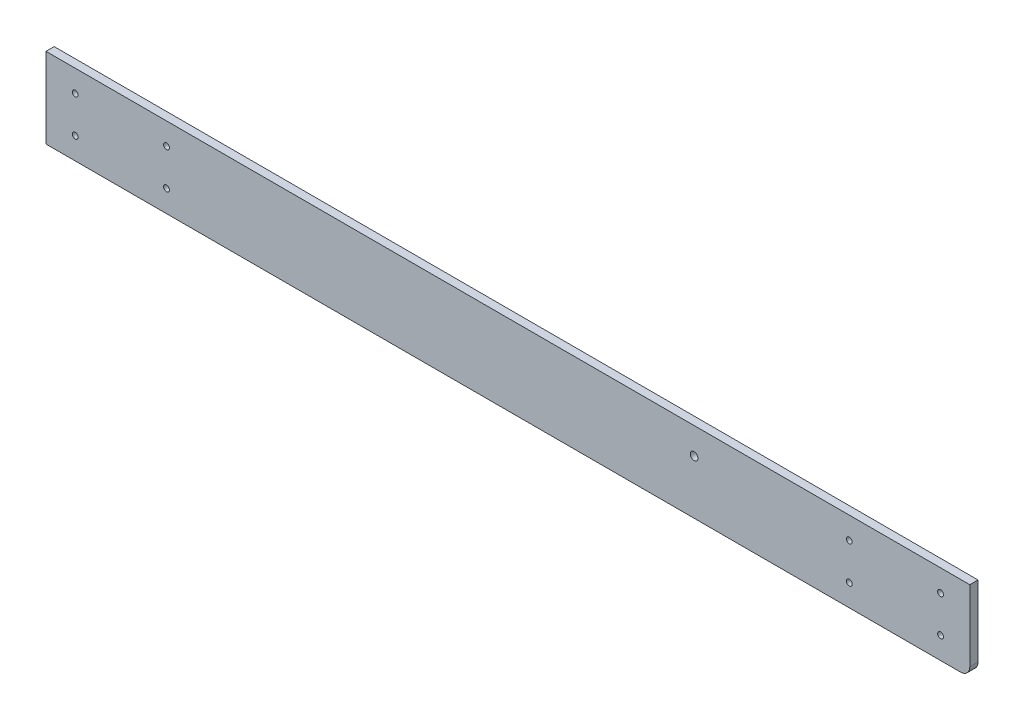
SolidWorks part; units mm, degrees
ref_plane "Front Plane" through (0, 0, 0) normal (0, 0, 1) x (1, 0, 0)
ref_plane "Top Plane" through (0, 0, 0) normal (0, 1, 0) x (1, 0, 0)
ref_plane "Right Plane" through (0, 0, 0) normal (1, 0, 0) x (0, 0, -1)
sketch "Sketch2" plane through (0, 0, 0) normal (0, 0, 1) x (1, 0, 0)
  line L0 (253, 0) -> (127, 0) construction
  line L1 (-253, -22) -> (253, -22)
  line L2 (-253, -22) -> (-253, 22)
  line L3 (-253, 22) -> (253, 22)
  line L4 (253, -22) -> (253, 22)
  line L5 (-253, -22) -> (253, 22) construction
  line L6 (-253, 22) -> (253, -22) construction
  line L7 (127, -1) -> (127, 9) construction
  line L8 (247, 3.3321) -> (247, 22) construction
  line L9 (0, 0) -> (0, 11.9613) construction
  circle A0 centre (102, 7.5) radius 2.1 construction
  circle A1 centre (102, 7.5) radius 2.1
  circle A2 centre (237, 10) radius 1.6
  circle A3 centre (187, 10) radius 1.6
  circle A6 centre (187, -10) radius 1.6
  circle A9 centre (237, -10) radius 1.6
  circle A10 centre (-187, 10) radius 1.6
  circle A11 centre (-187, -10) radius 1.6
  circle A12 centre (-237, -10) radius 1.6
  circle A13 centre (-237, 10) radius 1.6
  point P0 (0, 0)
  dimension "D3" = 10
  dimension "D5" = 3.2
  dimension "D1" = 44
  dimension "D2" = 506
  dimension "D4" = 10
  dimension "D6" = 2
  dimension "D7" = 2
extrude "Boss-Extrude1" add sketch "Sketch2" along normal blind 4.5
fillet "Fillet1" radius 5 1 edges at (253, -22, 2.25)
